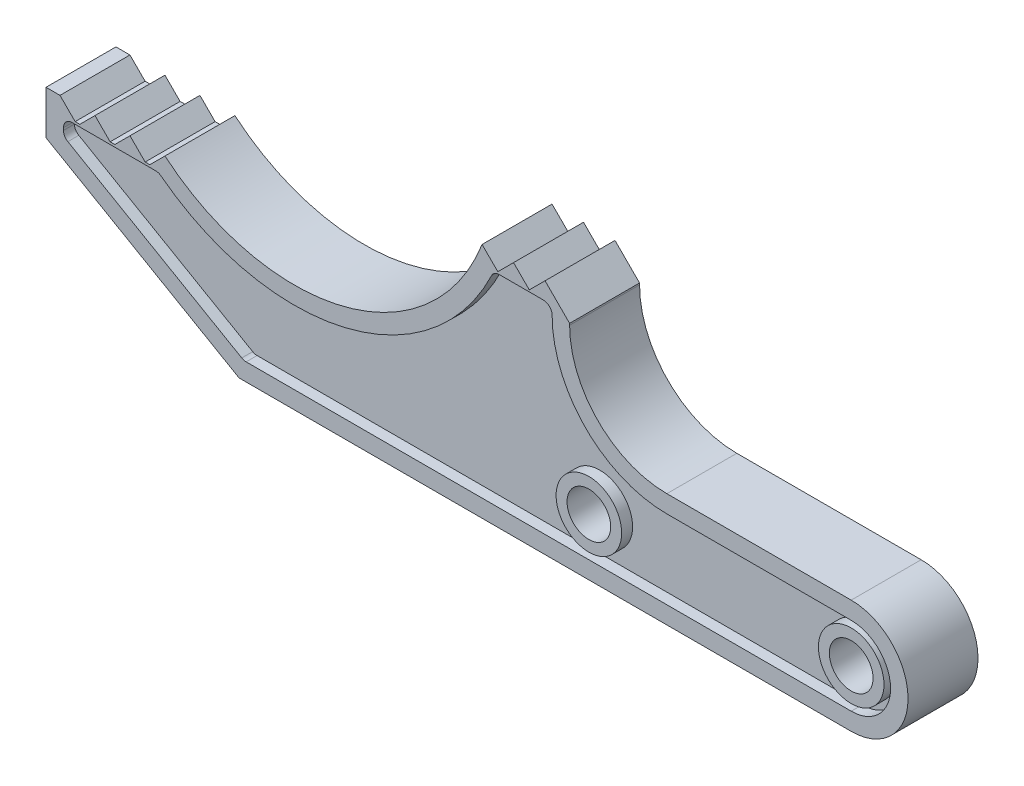
SolidWorks part; units mm, degrees
ref_plane "Front Plane" through (0, 0, 0) normal (0, 0, 1) x (1, 0, 0)
ref_plane "Top Plane" through (0, 0, 0) normal (0, 1, 0) x (1, 0, 0)
ref_plane "Right Plane" through (0, 0, 0) normal (1, 0, 0) x (0, 0, -1)
sketch "Sketch1" plane through (0, 0, 0) normal (0, 0, 1) x (1, 0, 0)
  line L0 (-35, 0) -> (35, 0)
  line L1 (-35, 0) -> (-57.0836, 12.75)
  line L2 (-57.0836, 12.75) -> (-57.0836, 17.75)
  line L3 (-57.0836, 17.75) -> (-43.4836, 17.75)
  line L4 (-7.2136, 27.12) -> (2.7964, 27.12)
  line L5 (35, 0) -> (35, 13) construction
  line L6 (35, 13) -> (13.9164, 13)
  line L7 (2.7964, 27.12) -> (2.7964, 24.12)
  arc A0 (-43.4836, 17.75) -> (-7.2136, 27.12) centre (-28.6874, 35.3588) ccw
  arc A1 (35, 0) -> (35, 13) centre (35, 6.5) ccw
  arc A2 (2.7964, 24.12) -> (13.9164, 13) centre (13.9164, 24.12) ccw
  point P4 (0, 0)
  dimension "D9" = 23
  dimension "D1" = 70
  dimension "D2" = 210
  dimension "D3" = 25.5
  dimension "D4" = 5
  dimension "D5" = 13.6
  dimension "D6" = 27.12
  dimension "D7" = 10.01
  dimension "D8" = 36.27
  dimension "D10" = 13
  dimension "D11" = 3
extrude "Boss-Extrude1" add sketch "Sketch1" along normal mid plane 8
sketch "Sketch2" plane through (0, 0, -4) normal (0, 0, -1) x (-1, 0, 0)
  line L0 (-35, 6.5) -> (-5, 6.5) construction
  circle A0 centre (-35, 6.5) radius 2.5
  circle A1 centre (-5, 6.5) radius 2.5
  dimension "D1" = 5
  dimension "D2" = 5
  dimension "D3" = 30
extrude "Cut-Extrude1" cut sketch "Sketch2" against normal through all
sketch "Sketch3" plane through (0, 0, 4) normal (0, 0, 1) x (1, 0, 0)
  line L0 (-57.0836, 17.75) -> (-55.4836, 17.75) construction
  line L1 (-43.4836, 17.75) -> (-57.0836, 17.75) construction
  line L2 (-55.4836, 17.75) -> (-53.4825, 15.7489)
  line L3 (-53.4825, 15.7489) -> (-51.4814, 17.75)
  line L4 (-53.4825, 15.7489) -> (-45.6737, 15.7489) construction
  line L5 (-51.4814, 17.75) -> (-51.4814, 15.3095) construction
  line L6 (-49.4803, 15.7489) -> (-51.4814, 17.75)
  line L7 (-47.4792, 17.75) -> (-49.4803, 15.7489)
  line L8 (-47.4792, 17.75) -> (-47.4792, 15.75) construction
  line L9 (-47.4792, 17.75) -> (-45.4781, 15.7489)
  line L10 (-45.4781, 15.7489) -> (-43.477, 17.75)
  line L21 (-44.1953, 15.75) -> (-55.0836, 15.75)
  line L22 (-55.0836, 15.75) -> (-55.0836, 13.9047)
  line L23 (-55.0836, 13.9047) -> (-34.4641, 2)
  line L24 (-34.4641, 2) -> (35, 2)
  line L25 (35, 11) -> (13.9164, 11)
  line L26 (0.7964, 24.12) -> (0.7964, 25.12)
  line L27 (0.7964, 25.12) -> (-5.8802, 25.12)
  line L28 (-44.1953, 15.75) -> (-55.0836, 15.75)
  line L29 (-55.0836, 15.75) -> (-55.0836, 13.9047)
  line L30 (-55.0836, 13.9047) -> (-34.4641, 2)
  line L31 (-34.4641, 2) -> (35, 2)
  line L32 (35, 11) -> (13.9164, 11)
  line L33 (0.7964, 24.12) -> (0.7964, 25.12)
  line L34 (0.7964, 25.12) -> (-5.8802, 25.12)
  arc A9 (-44.1953, 15.75) -> (-5.8802, 25.12) centre (-28.6874, 35.3588) ccw
  arc A10 (35, 2) -> (35, 11) centre (35, 6.5) ccw
  arc A11 (0.7964, 24.12) -> (13.9164, 11) centre (13.9164, 24.12) ccw
  arc A12 (-44.1953, 15.75) -> (-5.8802, 25.12) centre (-28.6874, 35.3588) ccw
  arc A13 (35, 2) -> (35, 11) centre (35, 6.5) ccw
  arc A14 (0.7964, 24.12) -> (13.9164, 11) centre (13.9164, 24.12) ccw
  dimension "D2" = 1.6
  dimension "D3" = 135
  dimension "D4" = 90
  dimension "D5" = 2.83
  dimension "D1" = 2
extrude "Cut-Extrude2" cut sketch "Sketch3" against normal blind 1.25 contours A12 L34 L33 A14 L32 A13 L31 L30 L29 L28
sketch "Sketch4" plane through (0, 0, 2.75) normal (0, 0, 1) x (1, 0, 0)
  circle A0 centre (35, 6.5) radius 2.5 construction
  circle A1 centre (5, 6.5) radius 2.5 construction
  circle A2 centre (35, 6.5) radius 2.5
  circle A3 centre (5, 6.5) radius 2.5
  circle A4 centre (5, 6.5) radius 3.75
  circle A5 centre (35, 6.5) radius 3.75
  dimension "D1" = 1.25
extrude "Boss-Extrude2" add sketch "Sketch4" along normal blind 1.25
mirror "Mirror1" about plane through (0, 0, 0) normal (0, 0, 1) of "Cut-Extrude2", "Boss-Extrude2"
sketch "Sketch6" plane through (0, 0, 4) normal (0, 0, 1) x (1, 0, 0)
  line L0 (-57.0836, 17.75) -> (-55.4836, 17.75) construction
  line L1 (-43.4836, 17.75) -> (-57.0836, 17.75) construction
  line L2 (-55.4836, 17.75) -> (-53.7506, 16.0169)
  line L3 (-53.2145, 16.0169) -> (-51.4814, 17.75)
  line L4 (-51.4814, 17.75) -> (-51.4814, 16.0169) construction
  line L5 (-49.7483, 16.0169) -> (-51.4814, 17.75)
  line L6 (-47.4792, 17.75) -> (-49.2123, 16.0169)
  line L8 (-47.4792, 17.75) -> (-45.7461, 16.0169)
  line L9 (-45.2101, 16.0169) -> (-43.477, 17.75)
  line L10 (-53.7506, 16.0169) -> (-53.2145, 16.0169)
  line L11 (-44.1953, 15.75) -> (-55.0836, 15.75) construction
  line L12 (-49.7483, 16.0169) -> (-49.2123, 16.0169)
  line L13 (-45.7461, 16.0169) -> (-45.2101, 16.0169)
  dimension "D1" = 1.6
  dimension "D3" = 135
  dimension "D4" = 0.2669
extrude "Cut-Extrude8" cut sketch "Sketch6" against normal through all and the other way through all
sketch "Sketch9" plane through (0, 0, 4) normal (0, 0, 1) x (1, 0, 0)
  line L0 (-9.3315, 25.32) -> (4.3982, 25.32) construction
  line L1 (0.7964, 25.12) -> (-5.8802, 25.12) construction
  line L2 (-7.2136, 27.12) -> (-5.4136, 25.32)
  line L3 (-5.4136, 25.32) -> (-3.6136, 27.12)
  line L4 (2.7964, 27.12) -> (-7.2136, 27.12) construction
  line L5 (-3.6136, 27.12) -> (-1.8136, 25.32)
  line L6 (-1.8136, 25.32) -> (-0.0136, 27.12)
  line L7 (-0.0136, 27.12) -> (2.7964, 24.31)
  line L8 (2.7964, 24.12) -> (2.7964, 27.12) construction
  dimension "D1" = 0.2
  dimension "D2" = 45
  dimension "D3" = 90
  dimension "D4" = 90
extrude "Cut-Extrude9" cut sketch "Sketch9" against normal through all and the other way through all
fillet "Fillet5" radius 1 1 edges at (-55.0836, 15.75, 3.375)
fillet "Fillet6" radius 1 2 edges at (-44.1953, 15.75, 3.375) (-55.0836, 13.9047, 3.375)
fillet "Fillet7" radius 1 3 edges at (0.7964, 25.12, 3.375) (-34.4641, 2, 3.375) (-5.8802, 25.12, 3.375)
fillet "Fillet8" radius 1 6 edges at (-55.0836, 13.9047, -3.375) (-34.4641, 2, -3.375) (-44.1953, 15.75, -3.375) (-55.0836, 15.75, -3.375) (-5.8802, 25.12, -3.375) (0.7964, 25.12, -3.375)
